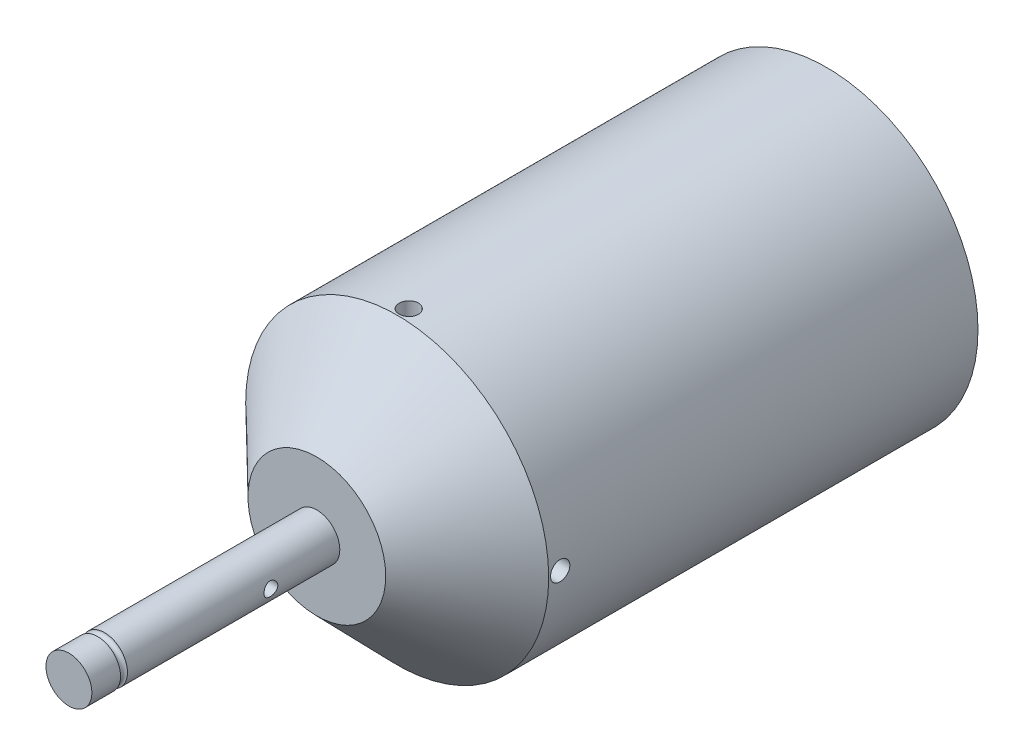
SolidWorks part; units mm, degrees
ref_plane "Front Plane" through (0, 0, 0) normal (0, 0, 1) x (1, 0, 0)
ref_plane "Top Plane" through (0, 0, 0) normal (0, 1, 0) x (1, 0, 0)
ref_plane "Right Plane" through (0, 0, 0) normal (1, 0, 0) x (0, 0, -1)
sketch "Sketch1" plane through (0, 0, 0) normal (0, 0, 1) x (1, 0, 0)
  circle A0 centre (0, 0) radius 33
  dimension "D1" = 66
extrude "Boss-Extrude1" add sketch "Sketch1" against normal mid plane 93.5
sketch "Sketch10" plane through (0, 0, 0) normal (1, 0, 0) x (0, 0, -1)
  line L0 (-64.25, 0) -> (-64.25, 15)
  line L1 (-46.75, 33) -> (-64.25, 15)
  line L2 (-1000, 0) -> (49000, 0) construction
  line L3 (-64.25, 0) -> (-46.75, 0)
  line L4 (-46.75, 0) -> (-46.75, 33)
  line L5 (46.75, -33) -> (46.75, 33) construction
  point P3 (-64.25, 0)
  dimension "D1" = 15
  dimension "D2" = 111
revolve "Revolve1" add sketch "Sketch10" angle 360 about L2
ref_plane "Plane1" through (0, 33, 0) normal (0, 1, 0) x (1, 0, 0)
sketch "Sketch11" plane through (-33, 33, 0) normal (0, -1, 0) x (0, 0, -1)
  line L0 (-64.25, 33) -> (46.75, 33) construction
  line L2 (-64.25, 48) -> (-64.25, 18) construction
  line L3 (46.75, 0) -> (46.75, 66) construction
  circle A0 centre (-44.25, 33) radius 2.1
  dimension "D1" = 4.2
  dimension "D2" = 91
extrude "Cut-Extrude1" cut sketch "Sketch11" along normal blind 10 and the other way through all
pattern_circular "CirPattern1" count 4 over 360 about axis through (0, 0, 46.75) along (0, 0, 1) of "Cut-Extrude1"
sketch "Sketch12" plane through (0, 0, 64.25) normal (0, 0, 1) x (1, 0, 0)
  circle A0 centre (0, 0) radius 5
  dimension "D1" = 10
extrude "Boss-Extrude5" add sketch "Sketch12" along normal blind 54
sketch "Sketch13" plane through (0, 0, 0) normal (1, 0, 0) x (0, 0, -1)
  line L0 (-118.25, 5) -> (-118.25, -5) construction
  circle A0 centre (-79.25, 0) radius 1.5
  dimension "D1" = 3
  dimension "D2" = 39
extrude "Cut-Extrude2" cut sketch "Sketch13" against normal through all both and the other way through all
sketch "Sketch14" plane through (0, 0, 0) normal (1, 0, 0) x (0, 0, -1)
  line L0 (-64.25, 5) -> (-118.25, 5) construction
  line L1 (-118.25, 5) -> (-118.25, -5) construction
  circle A0 centre (-111.25, 5) radius 0.75
  dimension "D1" = 1.5
  dimension "D2" = 7
revolve "Cut-Revolve1" cut sketch "Sketch14" angle 360 about axis through (0, 0, 118.25) along (0, 0, -1)
sketch "Sketch15" plane through (0, 0, -46.75) normal (0, 0, -1) x (-1, 0, 0)
  circle A0 centre (0, 0) radius 46.534
extrude "Cut-Extrude5" [suppressed] cut sketch "Sketch15" along normal blind 10 from offset 3 offset against normal yes
shell "Shell1" [suppressed] thickness 1.5
sketch "Sketch16" [suppressed] plane through (0, 0, 0) normal (0, 1, 0) x (1, 0, 0)
  line L5 (21.5, -41.7863) -> (21.5, -40.65)
  line L6 (21.5, -40.65) -> (21.5, -47.85) construction
  line L7 (21.5, -40.65) -> (32.0238, -30.1262)
  line L8 (32.0238, -30.1262) -> (32.0238, -41.7863)
  line L9 (32.0238, -41.7863) -> (21.5, -41.7863)
  line L10 (31.5, -40.65) -> (21.5, -40.65) construction
  dimension "D1" = 45
extrude "Boss-Extrude7" [suppressed] add sketch "Sketch16" along normal mid plane 1.5
pattern_circular "CirPattern2" [suppressed] count 4 over 360 of bodies 120
sketch "Sketch17" [suppressed] plane through (0, 0, 62.75) normal (0, 0, -1) x (-1, 0, 0)
  circle A0 centre (0, 0) radius 3.5
extrude "Boss-Extrude9" [suppressed] add sketch "Sketch17" against normal blind 1.5
chamfer "Chamfer1" [suppressed] distance 0.5 angle 45
sketch "Sketch18" plane through (0, 0, -46.75) normal (0, 0, -1) x (-1, 0, 0)
  circle A0 centre (0, 0) radius 51.9919
extrude "Cut-Extrude6" [suppressed] cut sketch "Sketch18" against normal through all from offset 1.5 offset against normal yes
sketch "Sketch19" [suppressed] plane through (0, 0, -45.25) normal (0, 0, 1) x (1, 0, 0)
  circle A0 centre (0, 0) radius 31.5
  circle A1 centre (0, 0) radius 33 construction
  dimension "D1" = 1.5
extrude "Boss-Extrude10" [suppressed] add sketch "Sketch19" along normal blind 10
shell "Shell2" [suppressed] thickness 1.5
